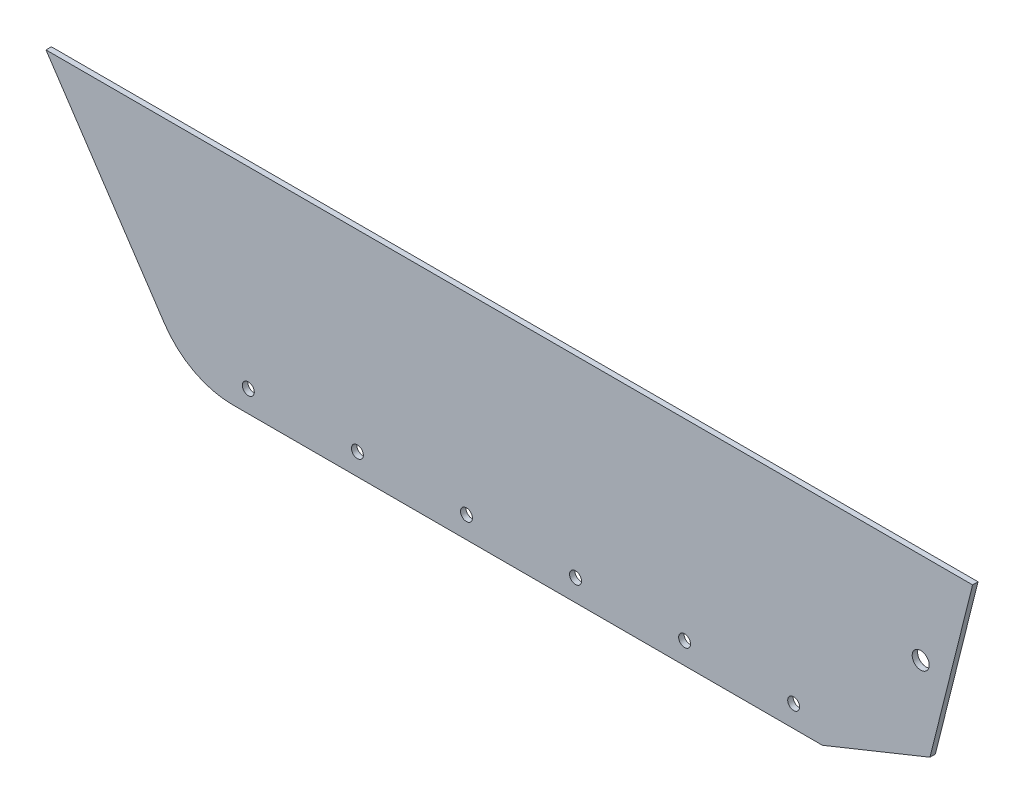
SolidWorks part; units mm, degrees
material "5052-H34"
ref_plane "Front Plane" through (0, 0, 0) normal (0, 0, 1) x (1, 0, 0)
ref_plane "Top Plane" through (0, 0, 0) normal (0, 1, 0) x (1, 0, 0)
ref_plane "Right Plane" through (0, 0, 0) normal (1, 0, 0) x (0, 0, -1)
sketch "Sketch1" plane through (0, 0, 0) normal (0, 0, 1) x (1, 0, 0)
  line L6 (-98.8794, 3.851) -> (-31.8794, -96.649)
  line L7 (428.1206, 28.9396) -> (403.1206, -71.149)
  line L9 (403.1206, -71.149) -> (366, -96.649)
  line L10 (-31.8794, -96.649) -> (366, -96.649)
  line L12 (-98.8794, 3.851) -> (-115.6052, 28.9396)
  line L13 (-115.6052, 28.9396) -> (428.1206, 28.9396)
  circle A0 centre (3.1206, -83.899) radius 3.5
  circle A1 centre (67.1206, -83.899) radius 3.5
  circle A2 centre (131.1206, -83.899) radius 3.5
  circle A3 centre (195.1206, -83.899) radius 3.5
  circle A4 centre (259.1206, -83.899) radius 3.5
  circle A5 centre (323.1206, -83.899) radius 3.5
  point P0 (-48.8794, -71.149)
  point P2 (-31.8794, -96.649)
  point P8 (48, -83.899)
  point P9 (403.1206, -71.149)
  dimension "D2" = 64
  dimension "D4" = 64
  dimension "D14" = 7
  dimension "D1" = 25.5
  dimension "D3" = 75
  dimension "D5" = 25
  dimension "D6" = 80
  dimension "D7" = 527
  dimension "D8" = 180
  dimension "D9" = 64
  dimension "D10" = 64
  dimension "D11" = 64
  dimension "D12" = 123.69
  dimension "D13" = 12.75
  dimension "D15" = 366
  dimension "D16" = 115.6052
extrude "Boss-Extrude1" add sketch "Sketch1" along normal blind 3.175 contours L12 L13 L7 L9 L10 L6
extrude "Cut-Extrude1" cut sketch "Sketch1<4>" along normal through all contours A0 | A1 | A2 | A3 | A4 | A5 region at (3.1206, -83.899, 0)
sketch "Sketch1<4>" plane through (0, 0, 0) normal (0, 0, 1) x (1, 0, 0) same geometry as "Sketch1"
sketch "Sketch2" plane through (0, 0, 0) normal (0, 0, -1) x (-1, 0, 0)
  circle A0 centre (-291.1206, -83.899) radius 6.5
  circle A2 centre (-241.5603, -124.3932) radius 6.5
  circle A3 centre (-192, -83.899) radius 6.5
  circle A4 centre (-128, -83.899) radius 6.5
  circle A5 centre (-64, -83.899) radius 6.5
  circle A6 centre (0, -83.899) radius 6.5
  dimension "D2" = 0
  dimension "D3" = 64
  dimension "D4" = 64
  dimension "D5" = 64
  dimension "D6" = 64
  dimension "D7" = 64
  dimension "D8" = 13
  dimension "D1" = 32
sketch "Sketch5" plane through (0, 0, 0) normal (0, 0, -1) x (-1, 0, 0)
  line L0 (48.8794, -71.149) -> (-14.2353, -96.649)
  line L1 (31.8794, -96.649) -> (-366, -96.649) construction
  line L2 (-14.2353, -96.649) -> (31.8794, -96.649)
  line L3 (31.8794, -96.649) -> (48.8794, -71.149)
  line L6 (-366, -96.649) -> (-403.1206, -71.149)
  line L7 (-403.1206, -71.149) -> (-352, -71.149)
  line L9 (-352, -71.149) -> (-326.5, -96.649)
  line L11 (-366, -96.649) -> (-326.5, -96.649)
  dimension "D1" = 22
  dimension "D2" = 45
extrude "Cut-Extrude2" [suppressed] cut sketch "Sketch5" against normal up to next
sketch "Sketch6" plane through (0, 0, 3.175) normal (0, 0, 1) x (1, 0, 0)
  line L0 (-48.8794, -71.149) -> (14.2353, -96.649)
  line L1 (-31.8794, -96.649) -> (366, -96.649) construction
  line L2 (14.2353, -96.649) -> (-31.8794, -96.649)
  line L3 (-31.8794, -96.649) -> (-48.8794, -71.149)
  dimension "D1" = 158
fillet "Fillet1" radius 48 1 edges at (-31.8794, -96.649, 1.5875)
sketch "Sketch7" plane through (0, 0, 3.175) normal (0, 0, 1) x (1, 0, 0)
  line L0 (403.1206, -71.149) -> (340.0059, -96.649)
  line L1 (-31.8794, -96.649) -> (366, -96.649) construction
  line L2 (340.0059, -96.649) -> (366, -96.649)
  line L3 (366, -96.649) -> (403.1206, -71.149)
  dimension "D1" = 22
extrude "Cut-Extrude3" cut sketch "Sketch7" against normal blind 10
sketch "Sketch9" plane through (0, 0, 0) normal (0, 0, -1) x (-1, 0, 0)
  line L0 (-403.1206, -71.149) -> (48.8794, -71.149)
  line L1 (48.8794, -71.149) -> (48.8794, -114.9143)
  line L2 (48.8794, -114.9143) -> (-403.1206, -114.9143)
  line L3 (-403.1206, -114.9143) -> (-403.1206, -71.149)
sketch "Sketch11" plane through (0, 0, 0) normal (0, 0, -1) x (-1, 0, 0)
  circle A0 centre (-397.6786, -24.6104) radius 5
extrude "Cut-Extrude5" cut sketch "Sketch11" against normal up to next
